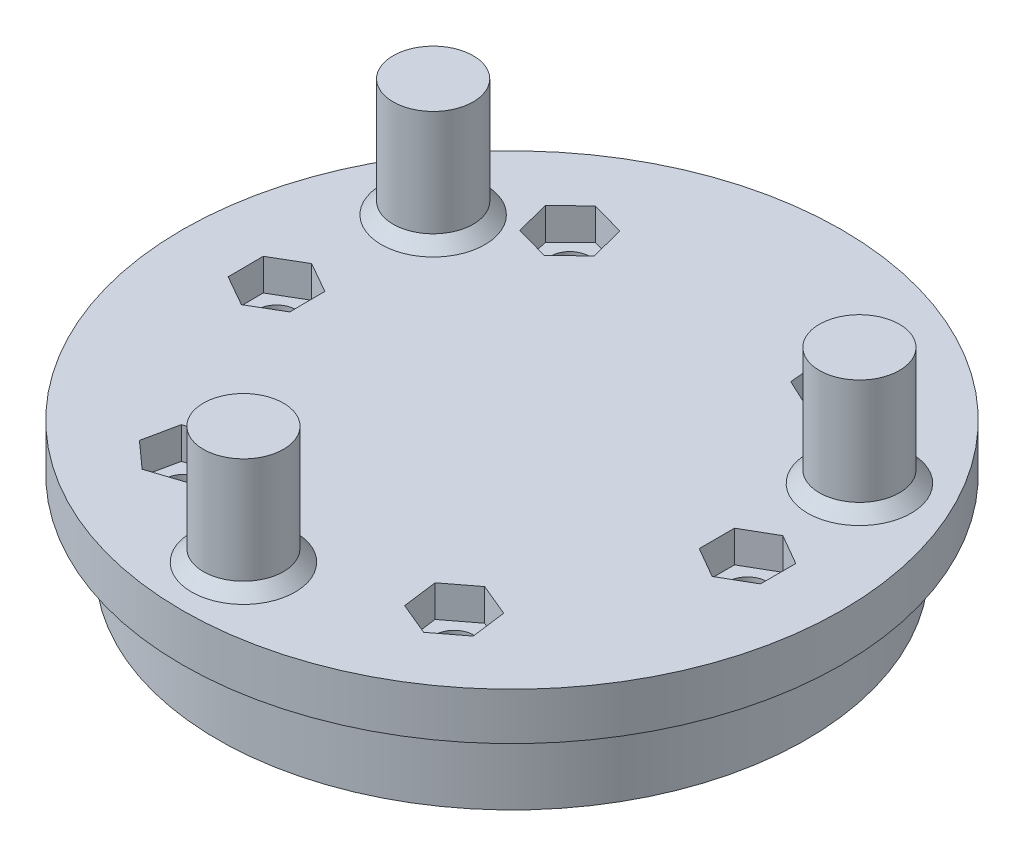
SolidWorks part; units mm, degrees
ref_plane "Front Plane" through (0, 0, 0) normal (0, 0, 1) x (1, 0, 0)
ref_plane "Top Plane" through (0, 0, 0) normal (0, 1, 0) x (1, 0, 0)
ref_plane "Right Plane" through (0, 0, 0) normal (1, 0, 0) x (0, 0, -1)
sketch "Sketch3" plane through (0, 0, 0) normal (0, 1, 0) x (1, 0, 0)
  circle A0 centre (0, 0) radius 28
  dimension "D1" = 56
extrude "Boss-Extrude1" add sketch "Sketch3" along normal blind 4
sketch "Sketch6" plane through (0, 0, 0) normal (0, -1, 0) x (1, 0, 0)
  circle A0 centre (0, 0) radius 25
  dimension "D1" = 50
extrude "Boss-Extrude4" add sketch "Sketch6" along normal blind 7
sketch "Sketch7" plane through (0, 4, 0) normal (0, 1, 0) x (1, 0, 0)
  line L0 (0, 0) -> (28, 0) construction
  line L1 (0, 0) -> (-17.3949, 11.0818) construction
  line L2 (0, 0) -> (-0.9542, -21.8542) construction
  line L3 (0, 0) -> (24.8363, 12.929) construction
  circle A0 centre (0, 0) radius 28 construction
  circle A8 centre (-0.9542, -21.8542) radius 3.4
  circle A9 centre (-18.4492, 11.7534) radius 3.4
  circle A10 centre (19.4034, 10.1008) radius 3.4
  point P17 (0, 0)
  dimension "D4" = 3
  dimension "D7" = 27.5
  dimension "D3" = 6.8
  dimension "D2" = 120
  dimension "D1" = 120
extrude "Boss-Extrude5" add sketch "Sketch7" along normal blind 10
sketch "Sketch8" plane through (0, 0, 0) normal (0, -1, 0) x (1, 0, 0)
  line L0 (0, 0) -> (20, 0) construction
  line L1 (0, 25) -> (0, -25) construction
  line L2 (0, 0) -> (11.4715, 16.383) construction
  line L3 (0, 0) -> (11.4715, -16.383) construction
  line L4 (0, 0) -> (-13.6508, -19.4954) construction
  line L5 (0, 0) -> (-20, 0) construction
  line L6 (0, 0) -> (-11.4715, -16.383) construction
  line L7 (0, 0) -> (-11.4715, 16.383) construction
  circle A0 centre (20, 0) radius 1.65
  circle A1 centre (0, 0) radius 25 construction
  circle A2 centre (0, 0) radius 25 construction
  circle A3 centre (-20, 0) radius 1.65
  circle A4 centre (11.4715, 16.383) radius 1.65
  circle A5 centre (-11.4715, -16.383) radius 1.65
  circle A6 centre (11.4715, -16.383) radius 1.65
  circle A7 centre (-11.4715, 16.383) radius 1.65
  dimension "D1" = 55
  dimension "D2" = 55
  dimension "D3" = 35
  dimension "D4" = 55
  dimension "D5" = 35
extrude "Cut-Extrude1" cut sketch "Sketch8" against normal through all and the other way blind 10
sketch "Sketch11" plane through (0, 4, 0) normal (0, 1, 0) x (1, 0, 0)
  line L1 (11.8581, -19.3603) -> (14.2432, -17.5369)
  line L2 (14.2432, -17.5369) -> (13.8566, -14.5597)
  line L3 (13.8566, -14.5597) -> (11.085, -13.4058)
  line L4 (11.085, -13.4058) -> (8.6999, -15.2292)
  line L5 (8.6999, -15.2292) -> (9.0865, -18.2064)
  line L6 (9.0865, -18.2064) -> (11.8581, -19.3603)
  line L7 (-12.0914, -19.3206) -> (-9.2375, -18.3886)
  line L8 (-9.2375, -18.3886) -> (-8.6176, -15.4511)
  line L9 (-8.6176, -15.4511) -> (-10.8516, -13.4455)
  line L10 (-10.8516, -13.4455) -> (-13.7056, -14.3774)
  line L11 (-13.7056, -14.3774) -> (-14.3254, -17.315)
  line L12 (-14.3254, -17.315) -> (-12.0914, -19.3206)
  line L13 (-22.5906, -1.5173) -> (-19.9813, -3.0022)
  line L14 (-19.9813, -3.0022) -> (-17.3907, -1.4849)
  line L15 (-17.3907, -1.4849) -> (-17.4094, 1.5173)
  line L16 (-17.4094, 1.5173) -> (-20.0187, 3.0022)
  line L17 (-20.0187, 3.0022) -> (-22.6093, 1.4849)
  line L18 (-22.6093, 1.4849) -> (-22.5906, -1.5173)
  line L19 (20, -3.0022) -> (22.6, -1.5011)
  line L20 (22.6, -1.5011) -> (22.6, 1.5011)
  line L21 (22.6, 1.5011) -> (20, 3.0022)
  line L22 (20, 3.0022) -> (17.4, 1.5011)
  line L23 (17.4, 1.5011) -> (17.4, -1.5011)
  line L24 (17.4, -1.5011) -> (20, -3.0022)
  line L25 (9.0083, 14.6668) -> (11.7262, 13.3916)
  line L26 (11.7262, 13.3916) -> (14.1895, 15.1079)
  line L27 (14.1895, 15.1079) -> (13.9348, 18.0993)
  line L28 (13.9348, 18.0993) -> (11.2168, 19.3744)
  line L29 (11.2168, 19.3744) -> (8.7536, 17.6582)
  line L30 (8.7536, 17.6582) -> (9.0083, 14.6668)
  line L31 (-10.7297, 13.4739) -> (-8.5812, 15.5709)
  line L32 (-8.5812, 15.5709) -> (-9.3231, 18.48)
  line L33 (-9.3231, 18.48) -> (-12.2134, 19.2922)
  line L34 (-12.2134, 19.2922) -> (-14.3618, 17.1952)
  line L35 (-14.3618, 17.1952) -> (-13.62, 14.286)
  line L36 (-13.62, 14.286) -> (-10.7297, 13.4739)
  circle A0 centre (11.4715, -16.383) radius 2.6 construction
  circle A1 centre (-11.4715, -16.383) radius 2.6 construction
  circle A2 centre (-20, 0) radius 2.6 construction
  circle A3 centre (20, 0) radius 2.6 construction
  circle A4 centre (11.4715, 16.383) radius 2.6 construction
  circle A5 centre (-11.4715, 16.383) radius 2.6 construction
  dimension "D1" = 5.2
extrude "Cut-Extrude3" cut sketch "Sketch11" against normal blind 2.7
chamfer "Chamfer1" distance 1 angle 45 3 edges at (19.4034, 4, -6.7008) (-18.4492, 4, -8.3534) (-0.9542, 4, 25.2542)
